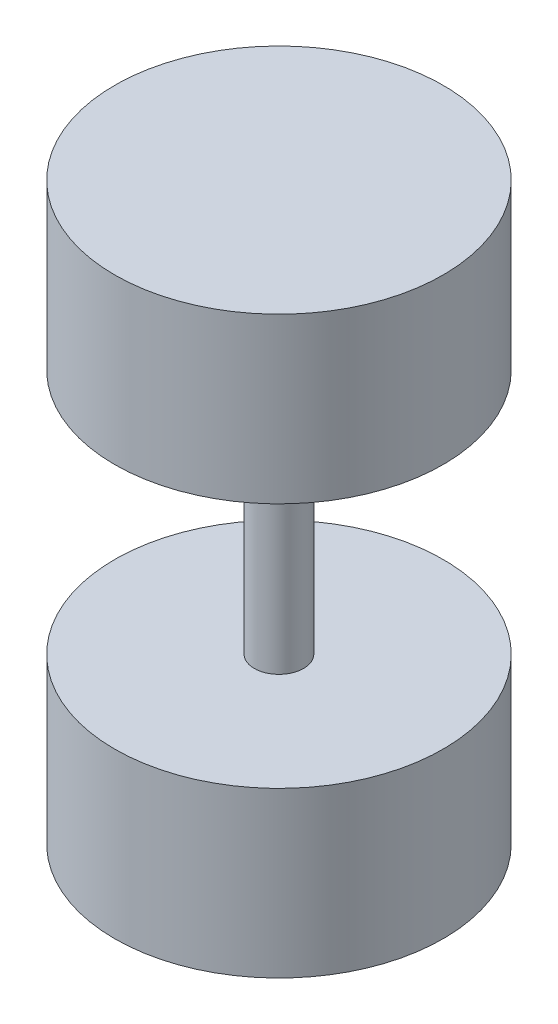
SolidWorks part; units mm, degrees
ref_plane "Front Plane" through (0, 0, 0) normal (0, 0, 1) x (1, 0, 0)
ref_plane "Top Plane" through (0, 0, 0) normal (0, 1, 0) x (1, 0, 0)
ref_plane "Right Plane" through (0, 0, 0) normal (1, 0, 0) x (0, 0, -1)
sketch "Sketch1" plane through (0, 0, 0) normal (0, 1, 0) x (1, 0, 0)
  circle A0 centre (0, 0) radius 10
  dimension "D1" = 20
extrude "Boss-Extrude1" add sketch "Sketch1" along normal blind 10
sketch "Sketch2" plane through (0, 10, 0) normal (0, 1, 0) x (1, 0, 0)
  circle A0 centre (0, 0) radius 1.5
  dimension "D1" = 3
extrude "Boss-Extrude2" add sketch "Sketch2" along normal blind 15
sketch "Sketch3" plane through (0, 0, 0) normal (0, -1, 0) x (1, 0, 0)
  line L1 (7, 0) -> (3.5, 6.0622)
  line L2 (3.5, 6.0622) -> (-3.5, 6.0622)
  line L3 (-3.5, 6.0622) -> (-7, 0)
  line L4 (-7, 0) -> (-3.5, -6.0622)
  line L5 (-3.5, -6.0622) -> (3.5, -6.0622)
  line L6 (3.5, -6.0622) -> (7, 0)
  circle A0 centre (0, 0) radius 6.0622 construction
  dimension "D1" = 7
extrude "Cut-Extrude1" cut sketch "Sketch3" against normal blind 8
ref_axis "Axis1" through (0, 10, 0) along (0, -1, 0)
sketch "Sketch4" plane through (0, 25, 0) normal (0, 1, 0) x (1, 0, 0)
  circle A0 centre (0, 0) radius 10
  circle A1 centre (0, 0) radius 10 construction
extrude "Boss-Extrude3" add sketch "Sketch4" along normal blind 10
